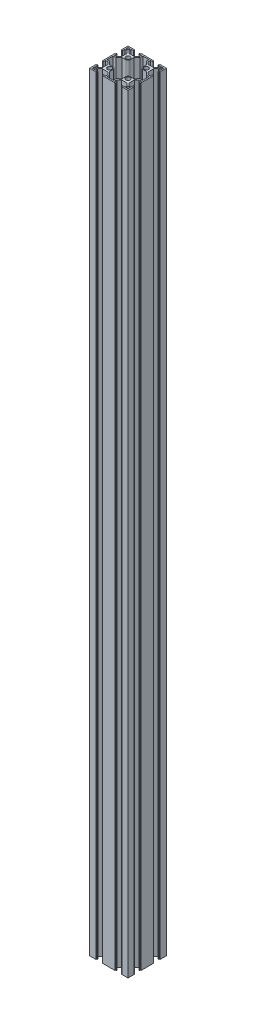
SolidWorks part; units mm, degrees
ref_plane "Front Plane" through (0, 0, 0) normal (0, 0, 1) x (1, 0, 0)
ref_plane "Top Plane" through (0, 0, 0) normal (0, 1, 0) x (1, 0, 0)
ref_plane "Right Plane" through (0, 0, 0) normal (1, 0, 0) x (0, 0, -1)
sketch "Sketch1" plane through (0, 0, 0) normal (0, 1, 0) x (1, 0, 0)
  line L0 (0, 30) -> (0, -30) construction
  line L1 (-30, -30) -> (30, -30)
  line L2 (-30, -30) -> (-30, 30)
  line L3 (-30, 30) -> (30, 30)
  line L4 (30, -30) -> (30, 30)
  line L5 (-30, -30) -> (30, 30) construction
  line L6 (-30, 30) -> (30, -30) construction
  line L7 (-30, 0) -> (30, 0) construction
  line L8 (-23.05, -28) -> (-6.95, -28)
  line L9 (-6.95, -28) -> (-6.95, -24.4)
  line L10 (-6.95, -24.4) -> (-10.615, -20.8)
  line L11 (-10.615, -20.8) -> (-19.385, -20.8)
  line L12 (-19.385, -20.8) -> (-23.05, -24.4)
  line L13 (-23.05, -24.4) -> (-23.05, -28)
  line L14 (10.615, -20.8) -> (19.385, -20.8)
  line L15 (6.95, -24.4) -> (10.615, -20.8)
  line L16 (6.95, -28) -> (6.95, -24.4)
  line L17 (23.05, -28) -> (6.95, -28)
  line L18 (23.05, -24.4) -> (23.05, -28)
  line L19 (19.385, -20.8) -> (23.05, -24.4)
  line L20 (19.385, 20.8) -> (23.05, 24.4)
  line L21 (23.05, 24.4) -> (23.05, 28)
  line L22 (23.05, 28) -> (6.95, 28)
  line L23 (6.95, 28) -> (6.95, 24.4)
  line L24 (6.95, 24.4) -> (10.615, 20.8)
  line L25 (10.615, 20.8) -> (19.385, 20.8)
  line L26 (-23.05, 24.4) -> (-23.05, 28)
  line L27 (-19.385, 20.8) -> (-23.05, 24.4)
  line L28 (-10.615, 20.8) -> (-19.385, 20.8)
  line L29 (-6.95, 24.4) -> (-10.615, 20.8)
  line L30 (-6.95, 28) -> (-6.95, 24.4)
  line L31 (-23.05, 28) -> (-6.95, 28)
  line L32 (-20.8, 19.385) -> (-24.4, 23.05)
  line L33 (-24.4, 23.05) -> (-28, 23.05)
  line L34 (-28, 23.05) -> (-28, 6.95)
  line L35 (-28, 6.95) -> (-24.4, 6.95)
  line L36 (-24.4, 6.95) -> (-20.8, 10.615)
  line L37 (-20.8, 10.615) -> (-20.8, 19.385)
  line L38 (-24.4, -23.05) -> (-28, -23.05)
  line L39 (-20.8, -19.385) -> (-24.4, -23.05)
  line L40 (-20.8, -10.615) -> (-20.8, -19.385)
  line L41 (-24.4, -6.95) -> (-20.8, -10.615)
  line L42 (-28, -6.95) -> (-24.4, -6.95)
  line L43 (-28, -23.05) -> (-28, -6.95)
  line L44 (20.8, -19.385) -> (24.4, -23.05)
  line L45 (24.4, -23.05) -> (28, -23.05)
  line L46 (28, -23.05) -> (28, -6.95)
  line L47 (28, -6.95) -> (24.4, -6.95)
  line L48 (24.4, -6.95) -> (20.8, -10.615)
  line L49 (20.8, -10.615) -> (20.8, -19.385)
  line L50 (24.4, 23.05) -> (28, 23.05)
  line L51 (20.8, 19.385) -> (24.4, 23.05)
  line L52 (20.8, 10.615) -> (20.8, 19.385)
  line L53 (24.4, 6.95) -> (20.8, 10.615)
  line L54 (28, 6.95) -> (24.4, 6.95)
  line L55 (28, 23.05) -> (28, 6.95)
  point P0 (0, 0)
  dimension "D1" = 60
  dimension "D2" = 16.1
  dimension "D3" = 8.77
  dimension "D4" = 3.6
  dimension "D5" = 7.2
  dimension "D6" = 2
  dimension "D7" = 6.95
extrude "Boss-Extrude1" add sketch "Sketch1" along normal blind 1200
sketch "Sketch2" plane through (0, 1200, 0) normal (0, 1, 0) x (1, 0, 0)
  line L0 (-19.1, -28) -> (-19.1, -29)
  line L1 (-23.05, -28) -> (-6.95, -28) construction
  line L2 (-30, -30) -> (30, -30) construction
  line L3 (-10.9, -28) -> (-10.9, -29)
  line L4 (-10.9, -29) -> (-9.9, -29)
  line L5 (-9.9, -29) -> (-9.9, -30)
  line L6 (-19.1, -29) -> (-20.1, -29)
  line L7 (-20.1, -29) -> (-20.1, -30)
  line L8 (-19.1, -28) -> (-10.9, -28)
  line L9 (-20.1, -30) -> (-9.9, -30)
  dimension "D1" = 8.2
  dimension "D2" = 3.95
  dimension "D3" = 1
  dimension "D4" = 1
extrude "Cut-Extrude1" cut sketch "Sketch2" against normal through all
mirror "Mirror1" about plane through (0, 0, 0) normal (1, 0, 0) of "Cut-Extrude1"
ref_axis "Axis1" through (0, 1050, 0) along (0, -1, 0)
pattern_circular "CirPattern1" count 4 over 360 about axis through (0, 1050, 0) along (0, -1, 0) of "Cut-Extrude1", "Mirror1"
sketch "Sketch4" plane through (0, 1200, 0) normal (0, 1, 0) x (1, 0, 0)
  line L0 (19.385, 18.8) -> (9.797, 18.8) construction
  line L1 (-18.8, 18.8) -> (-18.8, 9.797)
  line L2 (18.8, -19.385) -> (18.8, -9.797) construction
  line L3 (28, 4.95) -> (28, -4.95)
  line L4 (-18.8, -9.797) -> (-18.8, -19.385) construction
  line L5 (4.95, -28) -> (-4.95, -28)
  line L6 (-9.797, 18.8) -> (-9.797, 13.197)
  line L7 (-28, -4.95) -> (-28, 4.95)
  line L8 (-18.8, 9.797) -> (-23.5611, 4.95)
  line L9 (-23.5611, 4.95) -> (-28, 4.95)
  line L10 (18.8, 18.8) -> (9.797, 18.8)
  line L11 (9.797, 18.8) -> (4.95, 23.5611)
  line L12 (4.95, 23.5611) -> (4.95, 28)
  line L13 (4.95, 28) -> (4.95, 28)
  line L14 (4.95, 28) -> (4.95, 28)
  line L15 (4.95, 28) -> (4.95, 28)
  line L16 (4.95, 28) -> (4.95, 28)
  line L17 (4.95, 28) -> (-4.95, 28)
  line L18 (-4.95, 28) -> (-4.95, 28)
  line L19 (-4.95, 28) -> (-4.95, 28)
  line L20 (-4.95, 28) -> (-4.95, 28)
  line L21 (-4.95, 28) -> (-4.95, 28)
  line L22 (-4.95, 28) -> (-4.95, 23.5611)
  line L23 (-4.95, 23.5611) -> (-9.797, 18.8)
  line L24 (-9.797, 18.8) -> (-18.8, 18.8)
  line L25 (28, 4.95) -> (23.5611, 4.95)
  line L26 (23.5611, 4.95) -> (18.8, 9.797)
  line L27 (18.8, 9.797) -> (18.8, 18.8)
  line L28 (18.8, -18.8) -> (18.8, -9.797)
  line L29 (18.8, -9.797) -> (23.5611, -4.95)
  line L30 (23.5611, -4.95) -> (28, -4.95)
  line L31 (4.95, -28) -> (4.95, -23.5611)
  line L32 (4.95, -23.5611) -> (9.797, -18.8)
  line L33 (9.797, -18.8) -> (18.8, -18.8)
  line L34 (-18.8, -18.8) -> (-9.797, -18.8)
  line L35 (-9.797, -18.8) -> (-4.95, -23.5611)
  line L36 (-4.95, -23.5611) -> (-4.95, -28)
  line L37 (-28, -4.95) -> (-23.5611, -4.95)
  line L38 (-23.5611, -4.95) -> (-18.8, -9.797)
  line L39 (-18.8, -9.797) -> (-18.8, -18.8)
  line L40 (-9.797, 18.8) -> (-19.385, 18.8) construction
  line L41 (-18.8, 19.385) -> (-18.8, 9.797) construction
  line L42 (18.8, 9.797) -> (18.8, 19.385) construction
  line L43 (9.797, -18.8) -> (19.385, -18.8) construction
  line L44 (-19.385, -18.8) -> (-9.797, -18.8) construction
  line L45 (-13.197, 9.797) -> (-18.8, 9.797)
  line L46 (9.797, 18.8) -> (9.797, 13.197)
  line L47 (13.197, 9.797) -> (18.8, 9.797)
  line L48 (-18.8, -9.797) -> (-13.197, -9.797)
  line L49 (-9.797, -13.197) -> (-9.797, -18.8)
  line L50 (9.797, -18.8) -> (9.797, -13.197)
  line L51 (13.197, -9.797) -> (18.8, -9.797)
  line L52 (-27.5, -28) -> (-24.9, -28)
  line L53 (24.9, -28) -> (27.5, -28)
  line L54 (24.4, -27.5) -> (24.4, -24.9)
  line L55 (24.9, -24.4) -> (27.5, -24.4)
  line L56 (28, -27.5) -> (28, -24.9)
  line L57 (24.4, -28) -> (28, -24.4) construction
  line L58 (24.4, -24.4) -> (28, -28) construction
  line L59 (-28, -24.9) -> (-28, -27.5)
  line L60 (-27.5, -24.4) -> (-24.9, -24.4)
  line L61 (-24.4, -24.9) -> (-24.4, -27.5)
  line L62 (-28, 27.5) -> (-28, 24.9)
  line L63 (-24.9, 28) -> (-27.5, 28)
  line L64 (-24.4, 27.5) -> (-24.4, 24.9)
  line L65 (-24.9, 24.4) -> (-27.5, 24.4)
  line L66 (27.5, 28) -> (24.9, 28)
  line L67 (28, 24.9) -> (28, 27.5)
  line L68 (27.5, 24.4) -> (24.9, 24.4)
  line L69 (24.4, 24.9) -> (24.4, 27.5)
  line L116 (28, 19.1) -> (29, 19.1)
  line L117 (29, 19.1) -> (29, 20.1)
  line L118 (29, 20.1) -> (30, 20.1)
  line L119 (30, 20.1) -> (30, 30)
  line L120 (30, 30) -> (20.1, 30)
  line L121 (20.1, 30) -> (20.1, 29)
  line L122 (20.1, 29) -> (19.1, 29)
  line L123 (19.1, 29) -> (19.1, 28)
  line L124 (19.1, 28) -> (23.05, 28)
  line L125 (23.05, 28) -> (23.05, 24.4)
  line L126 (23.05, 24.4) -> (19.385, 20.8)
  line L127 (19.385, 20.8) -> (10.615, 20.8)
  line L128 (10.615, 20.8) -> (6.95, 24.4)
  line L129 (6.95, 24.4) -> (6.95, 28)
  line L130 (6.95, 28) -> (10.9, 28)
  line L131 (10.9, 28) -> (10.9, 29)
  line L132 (10.9, 29) -> (9.9, 29)
  line L133 (9.9, 29) -> (9.9, 30)
  line L134 (9.9, 30) -> (-9.9, 30)
  line L135 (-9.9, 30) -> (-9.9, 29)
  line L136 (-9.9, 29) -> (-10.9, 29)
  line L137 (-10.9, 29) -> (-10.9, 28)
  line L138 (-10.9, 28) -> (-6.95, 28)
  line L139 (-6.95, 28) -> (-6.95, 24.4)
  line L140 (-6.95, 24.4) -> (-10.615, 20.8)
  line L141 (-10.615, 20.8) -> (-19.385, 20.8)
  line L142 (-19.385, 20.8) -> (-23.05, 24.4)
  line L143 (-23.05, 24.4) -> (-23.05, 28)
  line L144 (-23.05, 28) -> (-19.1, 28)
  line L145 (-19.1, 28) -> (-19.1, 29)
  line L146 (-19.1, 29) -> (-20.1, 29)
  line L147 (-20.1, 29) -> (-20.1, 30)
  line L148 (-20.1, 30) -> (-30, 30)
  line L149 (-30, 30) -> (-30, 20.1)
  line L150 (-30, 20.1) -> (-29, 20.1)
  line L151 (-29, 20.1) -> (-29, 19.1)
  line L152 (-29, 19.1) -> (-28, 19.1)
  line L153 (-28, 19.1) -> (-28, 23.05)
  line L154 (-28, 23.05) -> (-24.4, 23.05)
  line L155 (-24.4, 23.05) -> (-20.8, 19.385)
  line L156 (-20.8, 19.385) -> (-20.8, 10.615)
  line L157 (-20.8, 10.615) -> (-24.4, 6.95)
  line L158 (-24.4, 6.95) -> (-28, 6.95)
  line L159 (-28, 6.95) -> (-28, 10.9)
  line L160 (-28, 10.9) -> (-29, 10.9)
  line L161 (-29, 10.9) -> (-29, 9.9)
  line L162 (-29, 9.9) -> (-30, 9.9)
  line L163 (-30, 9.9) -> (-30, -9.9)
  line L164 (-30, -9.9) -> (-29, -9.9)
  line L165 (-29, -9.9) -> (-29, -10.9)
  line L166 (-29, -10.9) -> (-28, -10.9)
  line L167 (-28, -10.9) -> (-28, -6.95)
  line L168 (-28, -6.95) -> (-24.4, -6.95)
  line L169 (-24.4, -6.95) -> (-20.8, -10.615)
  line L170 (-20.8, -10.615) -> (-20.8, -19.385)
  line L171 (-20.8, -19.385) -> (-24.4, -23.05)
  line L172 (-24.4, -23.05) -> (-28, -23.05)
  line L173 (-28, -23.05) -> (-28, -19.1)
  line L174 (-28, -19.1) -> (-29, -19.1)
  line L175 (-29, -19.1) -> (-29, -20.1)
  line L176 (-29, -20.1) -> (-30, -20.1)
  line L177 (-30, -20.1) -> (-30, -30)
  line L178 (-30, -30) -> (-20.1, -30)
  line L179 (-20.1, -30) -> (-20.1, -29)
  line L180 (-20.1, -29) -> (-19.1, -29)
  line L181 (-19.1, -29) -> (-19.1, -28)
  line L182 (-19.1, -28) -> (-23.05, -28)
  line L183 (-23.05, -28) -> (-23.05, -24.4)
  line L184 (-23.05, -24.4) -> (-19.385, -20.8)
  line L185 (-19.385, -20.8) -> (-10.615, -20.8)
  line L186 (-10.615, -20.8) -> (-6.95, -24.4)
  line L187 (-6.95, -24.4) -> (-6.95, -28)
  line L188 (-6.95, -28) -> (-10.9, -28)
  line L189 (-10.9, -28) -> (-10.9, -29)
  line L190 (-10.9, -29) -> (-9.9, -29)
  line L191 (-9.9, -29) -> (-9.9, -30)
  line L192 (-9.9, -30) -> (9.9, -30)
  line L193 (9.9, -30) -> (9.9, -29)
  line L194 (9.9, -29) -> (10.9, -29)
  line L195 (10.9, -29) -> (10.9, -28)
  line L196 (10.9, -28) -> (6.95, -28)
  line L197 (6.95, -28) -> (6.95, -24.4)
  line L198 (6.95, -24.4) -> (10.615, -20.8)
  line L199 (10.615, -20.8) -> (19.385, -20.8)
  line L200 (19.385, -20.8) -> (23.05, -24.4)
  line L201 (23.05, -24.4) -> (23.05, -28)
  line L202 (23.05, -28) -> (19.1, -28)
  line L203 (19.1, -28) -> (19.1, -29)
  line L204 (19.1, -29) -> (20.1, -29)
  line L205 (20.1, -29) -> (20.1, -30)
  line L206 (20.1, -30) -> (30, -30)
  line L207 (30, -30) -> (30, -20.1)
  line L208 (30, -20.1) -> (29, -20.1)
  line L209 (29, -20.1) -> (29, -19.1)
  line L210 (29, -19.1) -> (28, -19.1)
  line L211 (28, -19.1) -> (28, -23.05)
  line L212 (28, -23.05) -> (24.4, -23.05)
  line L213 (24.4, -23.05) -> (20.8, -19.385)
  line L214 (20.8, -19.385) -> (20.8, -10.615)
  line L215 (20.8, -10.615) -> (24.4, -6.95)
  line L216 (24.4, -6.95) -> (28, -6.95)
  line L217 (28, -6.95) -> (28, -10.9)
  line L218 (28, -10.9) -> (29, -10.9)
  line L219 (29, -10.9) -> (29, -9.9)
  line L220 (29, -9.9) -> (30, -9.9)
  line L221 (30, -9.9) -> (30, 9.9)
  line L222 (30, 9.9) -> (29, 9.9)
  line L223 (29, 9.9) -> (29, 10.9)
  line L224 (29, 10.9) -> (28, 10.9)
  line L225 (28, 10.9) -> (28, 6.95)
  line L226 (28, 6.95) -> (24.4, 6.95)
  line L227 (24.4, 6.95) -> (20.8, 10.615)
  line L228 (20.8, 10.615) -> (20.8, 19.385)
  line L229 (20.8, 19.385) -> (24.4, 23.05)
  line L230 (24.4, 23.05) -> (28, 23.05)
  line L231 (28, 23.05) -> (28, 19.1)
  line L232 (28, 19.1) -> (29, 19.1)
  line L233 (29, 19.1) -> (29, 20.1)
  line L234 (29, 20.1) -> (30, 20.1)
  line L235 (30, 20.1) -> (30, 30)
  line L236 (30, 30) -> (20.1, 30)
  line L237 (20.1, 30) -> (20.1, 29)
  line L238 (20.1, 29) -> (19.1, 29)
  line L239 (19.1, 29) -> (19.1, 28)
  line L240 (19.1, 28) -> (23.05, 28)
  line L241 (23.05, 28) -> (23.05, 24.4)
  line L242 (23.05, 24.4) -> (19.385, 20.8)
  line L243 (19.385, 20.8) -> (10.615, 20.8)
  line L244 (10.615, 20.8) -> (6.95, 24.4)
  line L245 (6.95, 24.4) -> (6.95, 28)
  line L246 (6.95, 28) -> (10.9, 28)
  line L247 (10.9, 28) -> (10.9, 29)
  line L248 (10.9, 29) -> (9.9, 29)
  line L249 (9.9, 29) -> (9.9, 30)
  line L250 (9.9, 30) -> (-9.9, 30)
  line L251 (-9.9, 30) -> (-9.9, 29)
  line L252 (-9.9, 29) -> (-10.9, 29)
  line L253 (-10.9, 29) -> (-10.9, 28)
  line L254 (-10.9, 28) -> (-6.95, 28)
  line L255 (-6.95, 28) -> (-6.95, 24.4)
  line L256 (-6.95, 24.4) -> (-10.615, 20.8)
  line L257 (-10.615, 20.8) -> (-19.385, 20.8)
  line L258 (-19.385, 20.8) -> (-23.05, 24.4)
  line L259 (-23.05, 24.4) -> (-23.05, 28)
  line L260 (-23.05, 28) -> (-19.1, 28)
  line L261 (-19.1, 28) -> (-19.1, 29)
  line L262 (-19.1, 29) -> (-20.1, 29)
  line L263 (-20.1, 29) -> (-20.1, 30)
  line L264 (-20.1, 30) -> (-30, 30)
  line L265 (-30, 30) -> (-30, 20.1)
  line L266 (-30, 20.1) -> (-29, 20.1)
  line L267 (-29, 20.1) -> (-29, 19.1)
  line L268 (-29, 19.1) -> (-28, 19.1)
  line L269 (-28, 19.1) -> (-28, 23.05)
  line L270 (-28, 23.05) -> (-24.4, 23.05)
  line L271 (-24.4, 23.05) -> (-20.8, 19.385)
  line L272 (-20.8, 19.385) -> (-20.8, 10.615)
  line L273 (-20.8, 10.615) -> (-24.4, 6.95)
  line L274 (-24.4, 6.95) -> (-28, 6.95)
  line L275 (-28, 6.95) -> (-28, 10.9)
  line L276 (-28, 10.9) -> (-29, 10.9)
  line L277 (-29, 10.9) -> (-29, 9.9)
  line L278 (-29, 9.9) -> (-30, 9.9)
  line L279 (-30, 9.9) -> (-30, -9.9)
  line L280 (-30, -9.9) -> (-29, -9.9)
  line L281 (-29, -9.9) -> (-29, -10.9)
  line L282 (-29, -10.9) -> (-28, -10.9)
  line L283 (-28, -10.9) -> (-28, -6.95)
  line L284 (-28, -6.95) -> (-24.4, -6.95)
  line L285 (-24.4, -6.95) -> (-20.8, -10.615)
  line L286 (-20.8, -10.615) -> (-20.8, -19.385)
  line L287 (-20.8, -19.385) -> (-24.4, -23.05)
  line L288 (-24.4, -23.05) -> (-28, -23.05)
  line L289 (-28, -23.05) -> (-28, -19.1)
  line L290 (-28, -19.1) -> (-29, -19.1)
  line L291 (-29, -19.1) -> (-29, -20.1)
  line L292 (-29, -20.1) -> (-30, -20.1)
  line L293 (-30, -20.1) -> (-30, -30)
  line L294 (-30, -30) -> (-20.1, -30)
  line L295 (-20.1, -30) -> (-20.1, -29)
  line L296 (-20.1, -29) -> (-19.1, -29)
  line L297 (-19.1, -29) -> (-19.1, -28)
  line L298 (-19.1, -28) -> (-23.05, -28)
  line L299 (-23.05, -28) -> (-23.05, -24.4)
  line L300 (-23.05, -24.4) -> (-19.385, -20.8)
  line L301 (-19.385, -20.8) -> (-10.615, -20.8)
  line L302 (-10.615, -20.8) -> (-6.95, -24.4)
  line L303 (-6.95, -24.4) -> (-6.95, -28)
  line L304 (-6.95, -28) -> (-10.9, -28)
  line L305 (-10.9, -28) -> (-10.9, -29)
  line L306 (-10.9, -29) -> (-9.9, -29)
  line L307 (-9.9, -29) -> (-9.9, -30)
  line L308 (-9.9, -30) -> (9.9, -30)
  line L309 (9.9, -30) -> (9.9, -29)
  line L310 (9.9, -29) -> (10.9, -29)
  line L311 (10.9, -29) -> (10.9, -28)
  line L312 (10.9, -28) -> (6.95, -28)
  line L313 (6.95, -28) -> (6.95, -24.4)
  line L314 (6.95, -24.4) -> (10.615, -20.8)
  line L315 (10.615, -20.8) -> (19.385, -20.8)
  line L316 (19.385, -20.8) -> (23.05, -24.4)
  line L317 (23.05, -24.4) -> (23.05, -28)
  line L318 (23.05, -28) -> (19.1, -28)
  line L319 (19.1, -28) -> (19.1, -29)
  line L320 (19.1, -29) -> (20.1, -29)
  line L321 (20.1, -29) -> (20.1, -30)
  line L322 (20.1, -30) -> (30, -30)
  line L323 (30, -30) -> (30, -20.1)
  line L324 (30, -20.1) -> (29, -20.1)
  line L325 (29, -20.1) -> (29, -19.1)
  line L326 (29, -19.1) -> (28, -19.1)
  line L327 (28, -19.1) -> (28, -23.05)
  line L328 (28, -23.05) -> (24.4, -23.05)
  line L329 (24.4, -23.05) -> (20.8, -19.385)
  line L330 (20.8, -19.385) -> (20.8, -10.615)
  line L331 (20.8, -10.615) -> (24.4, -6.95)
  line L332 (24.4, -6.95) -> (28, -6.95)
  line L333 (28, -6.95) -> (28, -10.9)
  line L334 (28, -10.9) -> (29, -10.9)
  line L335 (29, -10.9) -> (29, -9.9)
  line L336 (29, -9.9) -> (30, -9.9)
  line L337 (30, -9.9) -> (30, 9.9)
  line L338 (30, 9.9) -> (29, 9.9)
  line L339 (29, 9.9) -> (29, 10.9)
  line L340 (29, 10.9) -> (28, 10.9)
  line L341 (28, 10.9) -> (28, 6.95)
  line L342 (28, 6.95) -> (24.4, 6.95)
  line L343 (24.4, 6.95) -> (20.8, 10.615)
  line L344 (20.8, 10.615) -> (20.8, 19.385)
  line L345 (20.8, 19.385) -> (24.4, 23.05)
  line L346 (24.4, 23.05) -> (28, 23.05)
  line L347 (28, 23.05) -> (28, 19.1)
  circle A0 centre (14.2985, 14.2985) radius 3.4
  arc A1 (13.197, -9.797) -> (9.797, -13.197) centre (13.197, -13.197) ccw
  arc A2 (-9.797, -13.197) -> (-13.197, -9.797) centre (-13.197, -13.197) ccw
  arc A3 (13.197, 9.797) -> (9.797, 13.197) centre (13.197, 13.197) cw
  arc A4 (-9.797, 13.197) -> (-13.197, 9.797) centre (-13.197, 13.197) cw
  circle A5 centre (14.2985, -14.2985) radius 3.4
  circle A6 centre (-14.2985, -14.2985) radius 3.4
  circle A7 centre (-14.2985, 14.2985) radius 3.4
  arc A8 (24.4, -27.5) -> (24.9, -28) centre (24.9, -27.5) ccw
  arc A9 (28, -27.5) -> (27.5, -28) centre (27.5, -27.5) cw
  arc A10 (28, -24.9) -> (27.5, -24.4) centre (27.5, -24.9) ccw
  arc A11 (24.4, -24.9) -> (24.9, -24.4) centre (24.9, -24.9) cw
  arc A12 (-27.5, -28) -> (-28, -27.5) centre (-27.5, -27.5) cw
  arc A13 (-27.5, -24.4) -> (-28, -24.9) centre (-27.5, -24.9) ccw
  arc A14 (-24.9, -24.4) -> (-24.4, -24.9) centre (-24.9, -24.9) cw
  arc A15 (-24.9, -28) -> (-24.4, -27.5) centre (-24.9, -27.5) ccw
  arc A16 (-28, 27.5) -> (-27.5, 28) centre (-27.5, 27.5) cw
  arc A17 (-24.4, 27.5) -> (-24.9, 28) centre (-24.9, 27.5) ccw
  arc A18 (-24.4, 24.9) -> (-24.9, 24.4) centre (-24.9, 24.9) cw
  arc A19 (-28, 24.9) -> (-27.5, 24.4) centre (-27.5, 24.9) ccw
  arc A20 (27.5, 28) -> (28, 27.5) centre (27.5, 27.5) cw
  arc A21 (27.5, 24.4) -> (28, 24.9) centre (27.5, 24.9) ccw
  arc A22 (24.9, 24.4) -> (24.4, 24.9) centre (24.9, 24.9) cw
  arc A23 (24.9, 28) -> (24.4, 27.5) centre (24.9, 27.5) ccw
  point P102 (26.2, -26.2)
  point P104 (14.2985, 18.8)
  point P106 (18.8, 14.2985)
  point P140 (0, 0)
  point P239 (0, 0)
  dimension "D3" = 6.8
  dimension "D4" = 3.4
  dimension "D6" = 0.5
  dimension "D1" = 0
  dimension "D2" = 2
  dimension "D5" = 4
  dimension "D7" = 4
extrude "Cut-Extrude2" cut sketch "Sketch4" against normal through all contours L6 A4 L45 L8 L9 L7 L37 L38 L48 A2 L49 L35 L36 L5 L31 L32 L50 A1 L51 L29 L30 L3 L25 L26 L47 A3 L46 L11 L12 L17 L22 L23 | A7 | A0 | L66 A23 L69 A22 L68 A21 L67 A20 | L62 A19 L65 A18 L64 A17 L63 A16 | L52 A15 L61 A14 L60 A13 L59 A12 | A11 L54 A8 L53 A9 L56 A10 L55 | A6 | A5 region at (0, 1200, 0) region at (-26.2, 1200, 26.2) region at (26.2, 1200, 26.2) region at (-26.2, 1200, -26.2) region at (26.2, 1200, -26.2) region at (14.2985, 1200, -14.2985) region at (-14.2985, 1200, -14.2985)
fillet "Fillet1" radius 0.2 16 edges at (28, 600, -19.1) (30, 600, -20.1) (29, 600, -20.1) (29, 600, -19.1) (28, 600, 10.9) (29, 600, 9.9) (28, 600, 19.1) (29, 600, 20.1) (30, 600, 20.1) (29, 600, 19.1) (29, 600, 10.9) (30, 600, 9.9) (30, 600, -9.9) (29, 600, -9.9) (29, 600, -10.9) (28, 600, -10.9)
fillet "Fillet2" radius 0.2 20 edges at (-20.1, 0, -29.5) (-20.1, 1200, -29.5) (-20.1, 600, -29) (-19.6, 0, -29) (-19.1, 600, -29) (-19.6, 1200, -29) (-9.9, 600, -30) (-10.9, 600, -28) (-10.9, 600, -29) (-9.9, 600, -29) (19.1, 600, -28) (19.1, 600, -29) (20.1, 600, -29) (20.1, 600, -30) (10.9, 600, -28) (10.9, 600, -29) (9.9, 600, -29) (9.9, 600, -30) (-19.1, 600, -28) (-20.1, 600, -30)
fillet "Fillet3" radius 0.2 14 edges at (-29, 600, 9.9) (-29, 600, -20.1) (-30, 600, -20.1) (-29, 600, -19.1) (-28, 600, -10.9) (-29, 600, -10.9) (-29, 600, -9.9) (-30, 600, -9.9) (-29, 600, 10.9) (-30, 600, 9.9) (-28, 600, 19.1) (-29, 600, 19.1) (-29, 600, 20.1) (-30, 600, 20.1)
fillet "Fillet4" radius 0.2 16 edges at (-19.1, 600, 28) (10.9, 600, 28) (19.1, 600, 28) (20.1, 600, 29) (-10.9, 600, 28) (-9.9, 600, 29) (9.9, 600, 29) (-20.1, 600, 29) (19.1, 600, 29) (20.1, 600, 30) (10.9, 600, 29) (9.9, 600, 30) (-9.9, 600, 30) (-10.9, 600, 29) (-19.1, 600, 29) (-20.1, 600, 30)
